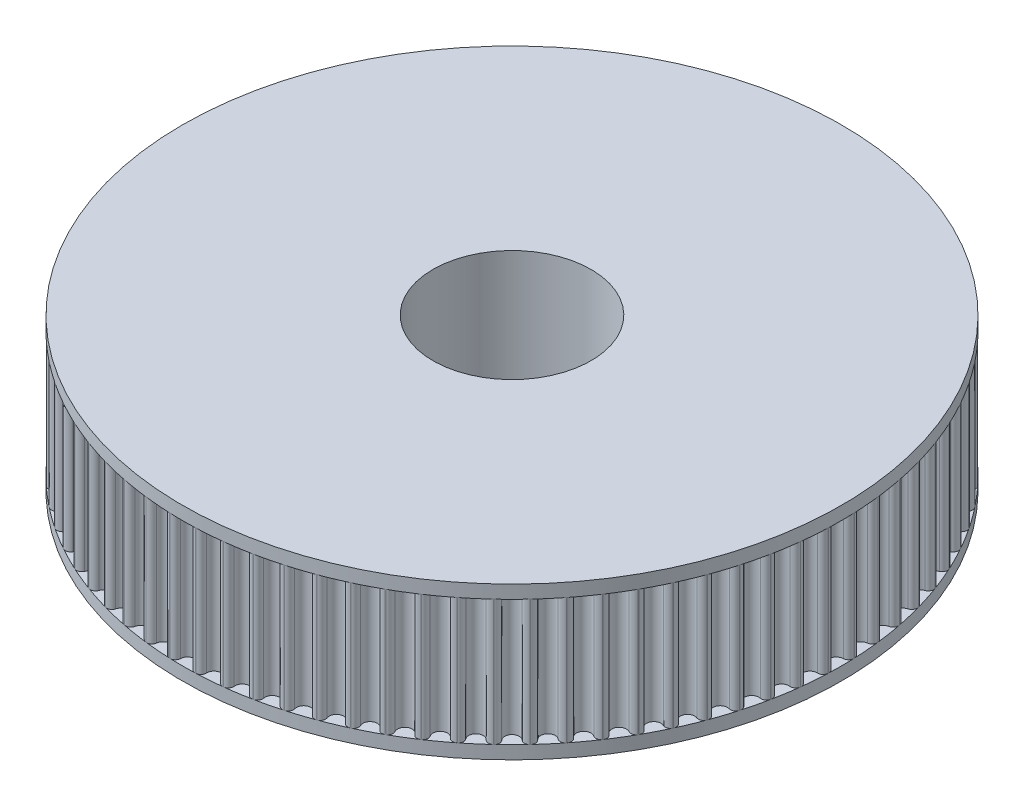
SolidWorks part; units mm, degrees
ref_plane "Front plan" through (0, 0, 0) normal (0, 0, 1) x (1, 0, 0)
ref_plane "Top plan" through (0, 0, 0) normal (0, 1, 0) x (1, 0, 0)
ref_plane "Right plan" through (0, 0, 0) normal (1, 0, 0) x (0, 0, -1)
sketch "Skica2" plane through (0, 0, 0) normal (0, 0, 1) x (1, 0, 0)
  line L1 (6, 4.775) -> (6, -4.775)
  line L3 (0, -9) -> (0, 9) construction
  line L7 (26, 3.775) -> (25, 3.775)
  line L8 (25, 3.775) -> (25, -3.775)
  line L9 (26, 3.775) -> (26, 4.775)
  line L12 (26, -4.775) -> (8.4518, -4.775)
  line L13 (26, 4.775) -> (6.1185, 4.775)
  line L14 (26, -4.775) -> (26, -3.775)
  line L15 (25, -3.775) -> (26, -3.775)
  line L17 (6.1185, 4.775) -> (6, 4.775)
  line L18 (8.4518, -4.775) -> (6, -4.775)
  point P3 (6, 0)
  point P7 (0, 0)
  dimension "D3" = 50
  dimension "D1" = 12
  dimension "D2" = 9.55
  dimension "D4" = 1
  dimension "D5" = 1
revolve "Revolute" add sketch "Skica2" angle 360 about L3 region at (15.609, 0, 0)
sketch "Sketch2" plane through (0, 3.775, 0) normal (0, -1, 0) x (1, 0, 0)
  line L0 (0, 0) -> (0, 24.6106) construction
  line L1 (0, 0) -> (8.4299, 23.5359) construction
  line L3 (0, 0) -> (-2.523, 24.8724) construction
  circle A1 centre (0, 0) radius 24.0606 construction
  circle A2 centre (0, 0) radius 24.6 construction
  arc A3 (-0.5497, 24.5939) -> (0.5497, 24.5939) centre (0, 24.6106) ccw
  arc A7 (-0.965, 24.9814) -> (-2.523, 24.8724) centre (0, 0) ccw
  arc A8 (0, 26.2332) -> (2.523, 24.8724) centre (0.9536, 24.9818) cw
  circle A9 centre (0, 0) radius 25 construction
  arc A10 (0.965, 24.9814) -> (2.523, 24.8724) centre (0, 0) cw
  arc A11 (0.965, 24.9814) -> (0.5497, 24.5939) centre (0.9496, 24.5817) ccw
  arc A12 (0, 26.2332) -> (-2.523, 24.8724) centre (-0.9536, 24.9818) ccw
  arc A13 (-0.965, 24.9814) -> (-0.5497, 24.5939) centre (-0.9496, 24.5817) cw
  dimension "D2" = 0.8
  dimension "D4" = 0.55
  dimension "D6" = 50
  dimension "D3" = 1.5733
  dimension "D1" = 0.4
extrude "Cut-Extrude3" cut sketch "Sketch2" along normal mid plane 50
pattern_circular "CirPattern1" count 80 over 360 about axis through (0, -9, 0) along (0, -1, 0) of "Cut-Extrude3"
ref_plane "Plane1" through (0, 1.575, 0) normal (0, -1, 0) x (-1, 0, 0)
sketch "Sketch3" plane through (0, 4.775, 0) normal (0, 1, 0) x (1, 0, 0)
  circle A0 centre (0, 0) radius 25
  circle A1 centre (0, 0) radius 6
  circle A2 centre (0, 0) radius 6 construction
extrude "Boss-Extrude1" add sketch "Sketch3" along normal blind 1
mirror "Mirror1" about plane through (0, 0, 0) normal (0, 1, 0) of "Boss-Extrude1"
equation "\"`\"=2"
equation "\"D6@Sketch2\"= \"D3@Skica2\""
